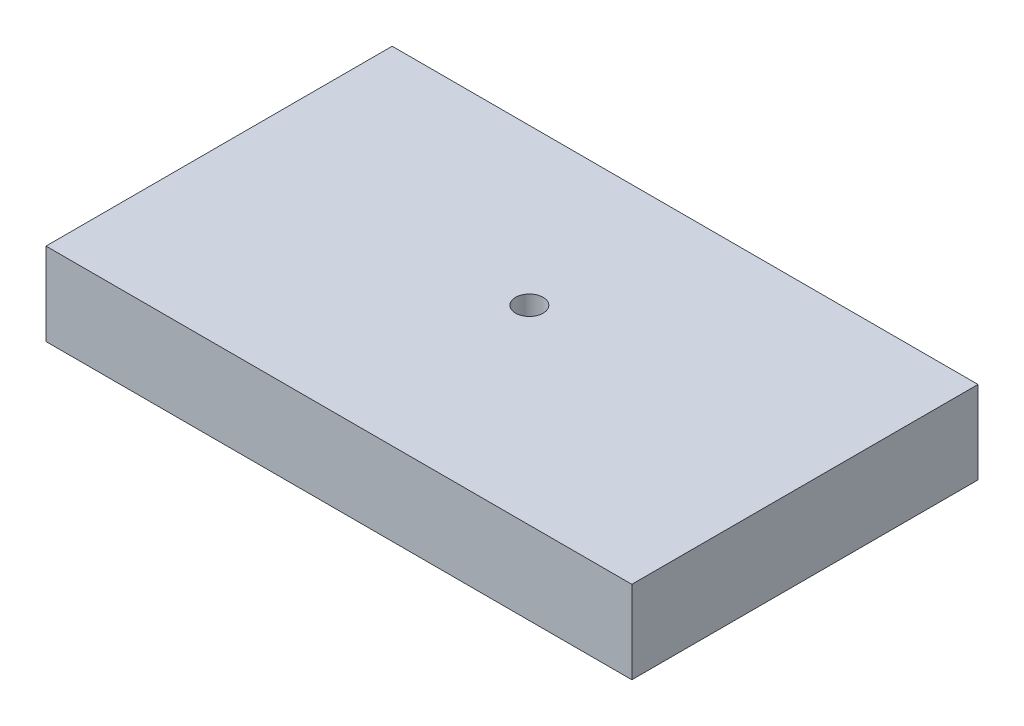
SolidWorks part; units mm, degrees
ref_plane "Front Plane" through (0, 0, 0) normal (0, 0, 1) x (1, 0, 0)
ref_plane "Top Plane" through (0, 0, 0) normal (0, 1, 0) x (1, 0, 0)
ref_plane "Right Plane" through (0, 0, 0) normal (1, 0, 0) x (0, 0, -1)
sketch "Sketch1" plane through (0, 0, 0) normal (0, 1, 0) x (1, 0, 0)
  line L0 (0, 0) -> (21.25, 0)
  line L1 (21.25, 0) -> (21.25, 25.1126)
  line L2 (21.25, 25.1126) -> (-21.25, 25.1126)
  line L3 (-21.25, 25.1126) -> (-21.25, 0)
  line L4 (-21.25, 0) -> (0, 0)
  line L5 (0, 0) -> (0, 25.1126) construction
  line L6 (-10.5, 19.1126) -> (-10.5, 25.1126)
  line L7 (10.5, 19.1126) -> (10.5, 25.1126)
  arc A0 (-10.5, 19.1126) -> (10.5, 19.1126) centre (0, 19.1126) ccw
  circle A1 centre (0, 13.8126) radius 1 construction
  circle A2 centre (0, 13.8126) radius 1
  dimension "D2" = 10.5
  dimension "D1" = 42.5
  dimension "D3" = 6
extrude "Boss-Extrude1" add sketch "Sketch1" along normal blind 3 contours L4 L5 A0 L6 L2 L3 | L5 L0 L1 L2 L7 A0 | A0 L5 L2 L6 | L5 A0 L7 L2 region at (12.8975, 0, -10.5152) region at (-12.8975, 0, -10.5152) region at (-4.8369, 0, -17.8387) region at (4.8369, 0, -17.8387)
extrude "Boss-Extrude2" add sketch "Sketch1<3>" against normal blind 3 contours L4 L5 A0 L6 L2 L3 | L5 L0 L1 L2 L7 A0 region at (12.8975, 0, -10.5152) region at (-12.8975, 0, -10.5152)
sketch "Sketch1<3>" plane through (0, 0, 0) normal (0, 1, 0) x (1, 0, 0) same geometry as "Sketch1"
